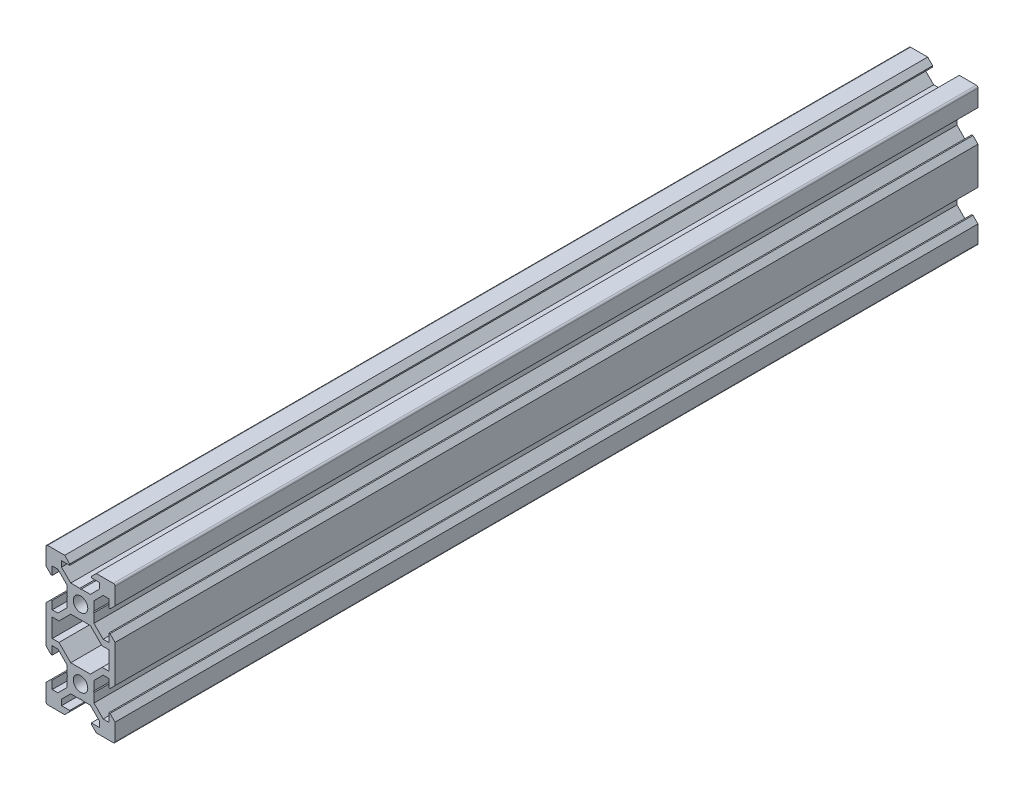
SolidWorks part; units mm, degrees
ref_plane "Plano frontal" through (0, 0, 0) normal (0, 0, 1) x (1, 0, 0)
ref_plane "Plano superior" through (0, 0, 0) normal (0, 1, 0) x (1, 0, 0)
ref_plane "Plano direito" through (0, 0, 0) normal (1, 0, 0) x (0, 0, -1)
sketch "Esboço1" plane through (0, 0, 0) normal (0, 0, 1) x (1, 0, 0)
  line L0 (8.2, -2.7) -> (8.2, 2.7)
  line L1 (8.2, 2.7) -> (6.2393, 2.7)
  line L2 (6.2393, 2.7) -> (2.8393, 6.1)
  line L3 (-2.8393, 6.1) -> (2.8393, 6.1)
  line L4 (-6.2393, 2.7) -> (-2.8393, 6.1)
  line L5 (-8.2, 2.7) -> (-6.2393, 2.7)
  line L6 (-8.2, -2.7) -> (-8.2, 2.7)
  line L7 (-8.2, -2.7) -> (-6.2393, -2.7)
  line L8 (-6.2393, -2.7) -> (-2.8393, -6.1)
  line L9 (-2.8393, -6.1) -> (2.8393, -6.1)
  line L10 (6.2393, -2.7) -> (2.8393, -6.1)
  line L11 (8.2, -2.7) -> (6.2393, -2.7)
  line L12 (3.9, 9.79) -> (3.69, 10)
  line L13 (3.69, 10) -> (3.9, 10.21)
  line L14 (3.9, 10.21) -> (3.9, 12.8393)
  line L15 (3.9, 12.8393) -> (6.5607, 15.5)
  line L16 (6.5607, 15.5) -> (8.2, 15.5)
  line L17 (8.2, 15.5) -> (8.2, 13.125)
  line L18 (8.2, 13.125) -> (8.545, 13.125)
  line L19 (8.545, 13.125) -> (10, 14.58)
  line L20 (10, 14.58) -> (10, 19.5)
  line L21 (9.5, 20) -> (4.58, 20)
  line L22 (4.58, 20) -> (3.125, 18.545)
  line L23 (3.125, 18.545) -> (3.125, 18.2)
  line L24 (3.125, 18.2) -> (5.5, 18.2)
  line L25 (5.5, 18.2) -> (5.5, 16.5607)
  line L26 (5.5, 16.5607) -> (2.8393, 13.9)
  line L27 (2.8393, 13.9) -> (0.21, 13.9)
  line L28 (0.21, 13.9) -> (0, 13.69)
  line L29 (0, 13.69) -> (-0.21, 13.9)
  line L30 (-0.21, 13.9) -> (-2.8393, 13.9)
  line L31 (-2.8393, 13.9) -> (-5.5, 16.5607)
  line L32 (-5.5, 16.5607) -> (-5.5, 18.2)
  line L33 (-5.5, 18.2) -> (-3.125, 18.2)
  line L34 (-3.125, 18.2) -> (-3.125, 18.545)
  line L35 (-3.125, 18.545) -> (-4.58, 20)
  line L36 (-4.58, 20) -> (-9.5, 20)
  line L37 (-10, 19.5) -> (-10, 14.58)
  line L38 (-10, 14.58) -> (-8.545, 13.125)
  line L39 (-8.545, 13.125) -> (-8.2, 13.125)
  line L40 (-8.2, 13.125) -> (-8.2, 15.5)
  line L41 (-8.2, 15.5) -> (-6.5607, 15.5)
  line L42 (-6.5607, 15.5) -> (-3.9, 12.8393)
  line L43 (-3.9, 12.8393) -> (-3.9, 10.21)
  line L44 (-3.9, 10.21) -> (-3.69, 10)
  line L45 (-3.69, 10) -> (-3.9, 9.79)
  line L46 (-3.9, 9.79) -> (-3.9, 7.1607)
  line L47 (-3.9, 7.1607) -> (-6.5607, 4.5)
  line L48 (-6.5607, 4.5) -> (-8.2, 4.5)
  line L49 (-8.2, 4.5) -> (-8.2, 6.875)
  line L50 (-8.2, 6.875) -> (-8.545, 6.875)
  line L51 (-8.545, 6.875) -> (-10, 5.42)
  line L52 (-10, 5.42) -> (-10, -5.42)
  line L53 (-10, -5.42) -> (-8.545, -6.875)
  line L54 (-8.545, -6.875) -> (-8.2, -6.875)
  line L55 (-8.2, -6.875) -> (-8.2, -4.5)
  line L56 (-8.2, -4.5) -> (-6.5607, -4.5)
  line L57 (-6.5607, -4.5) -> (-3.9, -7.1607)
  line L58 (-3.9, -7.1607) -> (-3.9, -9.79)
  line L59 (-3.9, -9.79) -> (-3.69, -10)
  line L60 (-3.69, -10) -> (-3.9, -10.21)
  line L61 (-3.9, -10.21) -> (-3.9, -12.8393)
  line L62 (-3.9, -12.8393) -> (-6.5607, -15.5)
  line L63 (-6.5607, -15.5) -> (-8.2, -15.5)
  line L64 (-8.2, -15.5) -> (-8.2, -13.125)
  line L65 (-8.2, -13.125) -> (-8.545, -13.125)
  line L66 (-8.545, -13.125) -> (-10, -14.58)
  line L67 (-10, -14.58) -> (-10, -19.5)
  line L68 (-9.5, -20) -> (-4.58, -20)
  line L69 (-4.58, -20) -> (-3.125, -18.545)
  line L70 (-3.125, -18.545) -> (-3.125, -18.2)
  line L71 (-3.125, -18.2) -> (-5.5, -18.2)
  line L72 (-5.5, -18.2) -> (-5.5, -16.5607)
  line L73 (-5.5, -16.5607) -> (-2.8393, -13.9)
  line L74 (-2.8393, -13.9) -> (-0.21, -13.9)
  line L75 (-0.21, -13.9) -> (0, -13.69)
  line L76 (0, -13.69) -> (0.21, -13.9)
  line L77 (0.21, -13.9) -> (2.8393, -13.9)
  line L78 (2.8393, -13.9) -> (5.5, -16.5607)
  line L79 (5.5, -16.5607) -> (5.5, -18.2)
  line L80 (5.5, -18.2) -> (3.125, -18.2)
  line L81 (3.125, -18.2) -> (3.125, -18.545)
  line L82 (3.125, -18.545) -> (4.58, -20)
  line L83 (4.58, -20) -> (9.5, -20)
  line L84 (10, -19.5) -> (10, -14.58)
  line L85 (10, -14.58) -> (8.545, -13.125)
  line L86 (8.545, -13.125) -> (8.2, -13.125)
  line L87 (8.2, -13.125) -> (8.2, -15.5)
  line L88 (8.2, -15.5) -> (6.5607, -15.5)
  line L89 (6.5607, -15.5) -> (3.9, -12.8393)
  line L90 (3.9, -12.8393) -> (3.9, -10.21)
  line L91 (3.9, -10.21) -> (3.69, -10)
  line L92 (3.69, -10) -> (3.9, -9.79)
  line L93 (3.9, -9.79) -> (3.9, -7.1607)
  line L94 (3.9, -7.1607) -> (6.5607, -4.5)
  line L95 (6.5607, -4.5) -> (8.2, -4.5)
  line L96 (8.2, -4.5) -> (8.2, -6.875)
  line L97 (8.2, -6.875) -> (8.545, -6.875)
  line L98 (8.545, -6.875) -> (10, -5.42)
  line L99 (10, -5.42) -> (10, 5.42)
  line L100 (10, 5.42) -> (8.545, 6.875)
  line L101 (8.545, 6.875) -> (8.2, 6.875)
  line L102 (8.2, 6.875) -> (8.2, 4.5)
  line L103 (8.2, 4.5) -> (6.5607, 4.5)
  line L104 (6.5607, 4.5) -> (3.9, 7.1607)
  line L105 (3.9, 7.1607) -> (3.9, 9.79)
  circle A0 centre (0, -10) radius 2.1
  circle A1 centre (0, 10) radius 2.1
  arc A2 (10, 19.5) -> (9.5, 20) centre (9.5, 19.5) ccw
  arc A3 (-9.5, 20) -> (-10, 19.5) centre (-9.5, 19.5) ccw
  arc A4 (-10, -19.5) -> (-9.5, -20) centre (-9.5, -19.5) ccw
  arc A5 (9.5, -20) -> (10, -19.5) centre (9.5, -19.5) ccw
extrude "Ressalto-extrusão1" add sketch "Esboço1" along normal blind 250
ref_plane "Plano2" through (0, 0, 0) normal (1, 0, 0) x (0, 0, -1)
ref_plane "Plano3" through (0, 0, 0) normal (0, 1, 0) x (1, 0, 0)
ref_plane "Plano4" through (0, 0, 125) normal (0, 0, -1) x (-1, 0, 0)
ref_plane "Plano5" through (0, 10, 0) normal (0, 1, 0) x (1, 0, 0)
ref_plane "Plano6" through (0, -10, 0) normal (0, 1, 0) x (1, 0, 0)
